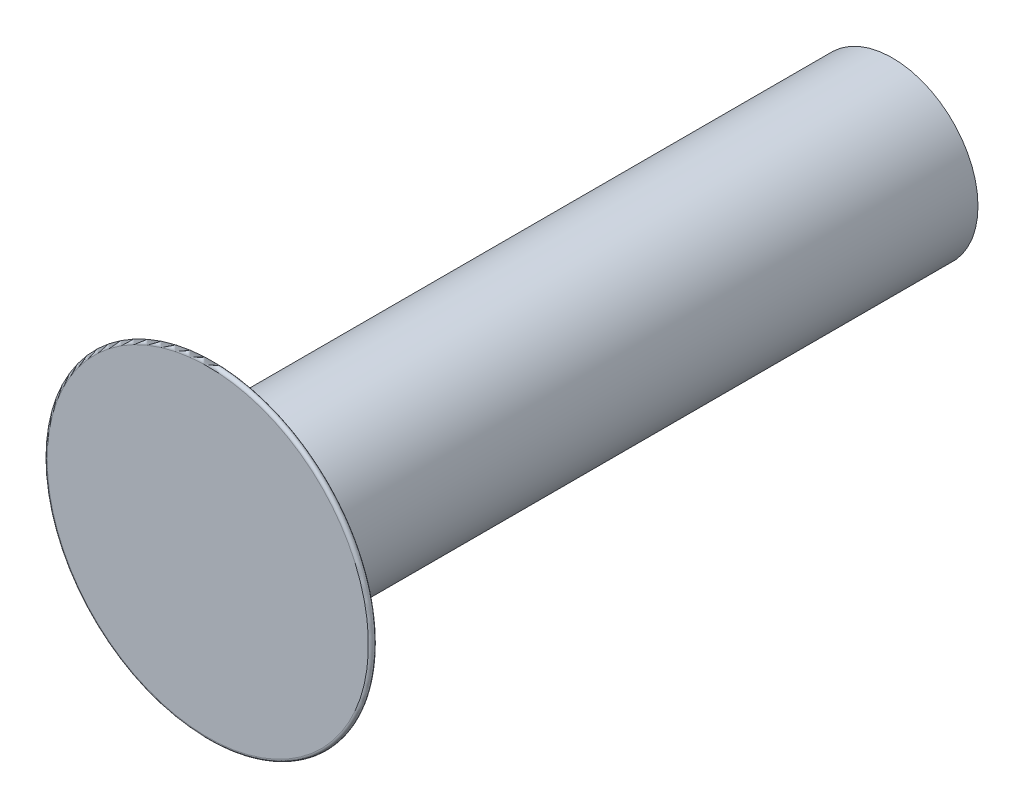
SolidWorks part; units mm, degrees
ref_plane "Front Plane" through (0, 0, 0) normal (0, 0, 1) x (1, 0, 0)
ref_plane "Top Plane" through (0, 0, 0) normal (0, 1, 0) x (1, 0, 0)
ref_plane "Right Plane" through (0, 0, 0) normal (1, 0, 0) x (0, 0, -1)
sketch "BaseBodySke" plane through (0, 0, 0) normal (0, 1, 0) x (1, 0, 0)
  line L0 (0, 0) -> (-6.35, 0)
  line L1 (0, 0) -> (0, 32.7778) construction
  line L2 (0, 0) -> (0, 25.4)
  line L3 (0, 25.4) -> (-3.175, 25.4)
  line L4 (-3.175, 1.8542) -> (-3.175, 25.4)
  line L5 (-6.35, 25.4) -> (-6.35, 0) construction
  line L6 (-6.35, -1.8542) -> (-6.35, 0) construction
  line L7 (-6.35, 0) -> (-3.175, 1.8542)
  line L9 (-3.175, 1.8542) -> (-3.175, 0) construction
  dimension "Head_Diameter" = 12.7
  dimension "Diameter" = 6.35
revolve "BaseBody" add sketch "BaseBodySke" angle 360 about L1
fillet "Fillet" radius 0.1058 1 edges at (6.35, 0, 0)
equation "\"D1@Fillet\" = \"Diameter@BaseBodySke\"/60"
